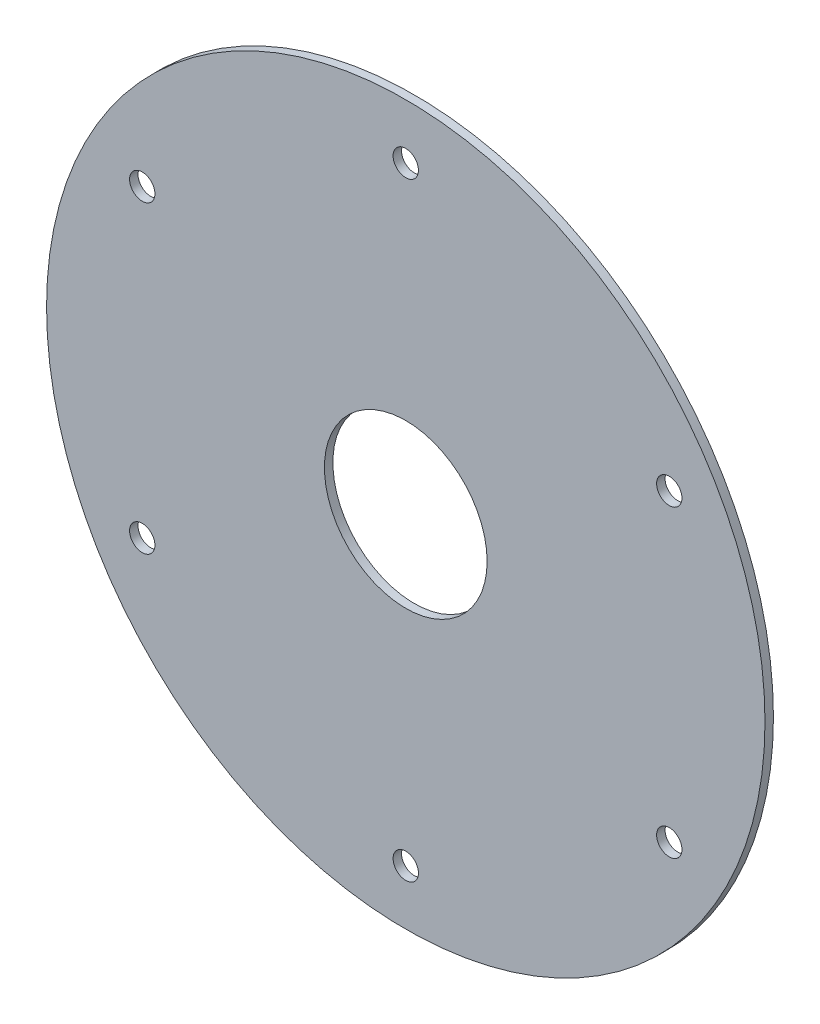
SolidWorks part; units mm, degrees
material "СТ3КП"
ref_plane "Спереди" through (0, 0, 0) normal (0, 0, 1) x (1, 0, 0)
ref_plane "Сверху" through (0, 0, 0) normal (0, 1, 0) x (1, 0, 0)
ref_plane "Справа" through (0, 0, 0) normal (1, 0, 0) x (0, 0, -1)
sketch "Эскиз1" plane through (0, 0, 0) normal (0, 0, 1) x (1, 0, 0)
  line L0 (0, 0) -> (0, 150) construction
  line L1 (0, 0) -> (0, 144) construction
  line L2 (0, 0) -> (124.7077, 72) construction
  line L3 (124.7077, 72) -> (0, 144) construction
  circle A0 centre (0, 0) radius 170
  circle A1 centre (0, 0) radius 38.5 construction
  circle A2 centre (0, 0) radius 38.5
  circle A3 centre (0, 144) radius 6
  circle A4 centre (124.7077, 72) radius 6
  circle A5 centre (124.7077, -72) radius 6
  circle A6 centre (0, -144) radius 6
  circle A7 centre (-124.7077, -72) radius 6
  circle A8 centre (-124.7077, 72) radius 6
  point P0 (97.1179, 41.7894)
  point P14 (0, 0)
  point P25 (0, 0)
  dimension "D1" = 6
base flange "Базовая кромка1" sketch "Эскиз1" thickness 4 reverse thickness direction yes parameters "D1"=1.5
sketch "Сгиб-Линии1" plane through (0, 0, 0) normal (0, 1, 0) x (1, 0, 0)
sketch "Граничная рамка1" plane through (0, 0, 0) normal (0, 1, 0) x (1, 0, 0)
sheet metal parameters "Листовой металл3" thickness 4 parameters "D1"=1.5
flat pattern "Развертка3" [suppressed]
sketch "Сгиб-Линии2" plane through (0, 0, 0) normal (0, 1, 0) x (1, 0, 0)
sketch "Граничная рамка2" [suppressed] plane through (0, 0, 0) normal (0, 1, 0) x (1, 0, 0)
